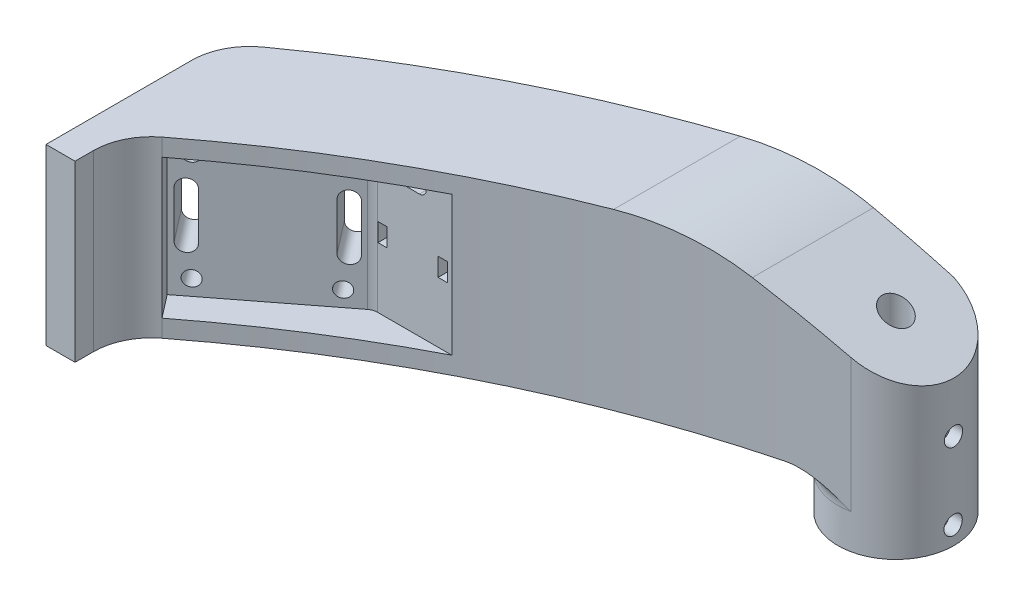
SolidWorks part; units mm, degrees
ref_plane "Front Plane" through (0, 0, 0) normal (0, 0, 1) x (1, 0, 0)
ref_plane "Top Plane" through (0, 0, 0) normal (0, 1, 0) x (1, 0, 0)
ref_plane "Right Plane" through (0, 0, 0) normal (1, 0, 0) x (0, 0, -1)
sketch "Sketch1" plane through (0, 0, 0) normal (0, 1, 0) x (1, 0, 0)
  line L1 (0, 0) -> (-86.36, -49.86) construction
  line L2 (0, 0) -> (-70.9465, 0) construction
  line L3 (0, 0) -> (0, -166.0504) construction
  line L4 (-86.36, -49.86) -> (-35.56, -49.86) construction
  line L5 (-86.36, -49.86) -> (-86.36, -100.66) construction
  line L6 (-86.36, -100.66) -> (-35.56, -100.66) construction
  line L7 (-35.56, -49.86) -> (-35.56, -100.66) construction
  line L8 (-86.36, -49.86) -> (-35.56, -100.66) construction
  line L9 (-86.36, -100.66) -> (-35.56, -49.86) construction
  line L10 (-105.41, -63.9265) -> (-105.41, -74.0865)
  line L11 (-105.41, -74.0865) -> (-111.76, -74.0865)
  line L12 (-111.76, -74.0865) -> (-111.76, -35.8449)
  circle A0 centre (0, 0) radius 12.7
  arc A1 (2.611, -12.4287) -> (-105.41, -63.9265) centre (54.83, -261.003) ccw
  arc A2 (-111.76, -35.8449) -> (0, 12.7) centre (42.7575, -238.6554) cw
  point P12 (-60.96, -75.26)
  dimension "D1" = 25.4
  dimension "D7" = 254
  dimension "D10" = 25.4
  dimension "D11" = 254.9662
  dimension "D2" = 30
  dimension "D3" = 50.8
  dimension "D4" = 50.8
  dimension "2.5" = 60.96
  dimension "D6" = 19.05
  dimension "D8" = 6.35
  dimension "D9" = 10.16
extrude "Boss-Extrude1" add sketch "Sketch1" along normal blind 38.1 contours A1 A0 L12 L11 L10 | A0 region at (-63.4576, 0, 24.428) region at (0.0025, 0, 0.0139)
sketch "Sketch3" plane through (0, 0, 0) normal (0, 0, 1) x (1, 0, 0)
  line L0 (-111.76, 19.05) -> (12.7, 19.05) construction
  line L1 (-111.76, 38.1) -> (-111.76, 0) construction
  line L2 (12.7, 0) -> (12.7, 38.1) construction
  line L4 (-115.2153, 16.5219) -> (-96.2951, 16.5219)
  line L5 (-115.2153, 16.5219) -> (-115.2153, 21.5781)
  line L6 (-115.2153, 21.5781) -> (-96.2951, 21.5781)
  line L7 (-96.2951, 16.5219) -> (-96.2951, 21.5781)
  line L8 (-115.2153, 16.5219) -> (-96.2951, 21.5781) construction
  line L9 (-115.2153, 21.5781) -> (-96.2951, 16.5219) construction
  point P6 (-105.7552, 19.05)
fillet "Fillet4" radius 12.7 1 edges at (-105.41, 19.05, 63.9265)
fillet "Fillet5" radius 12.7 1 edges at (-111.76, 19.05, 35.8449)
sketch "Sketch14" plane through (0, 0, 0) normal (0, -1, 0) x (1, 0, 0)
  circle A0 centre (0, 0) radius 10.125
  dimension "D1" = 20.25
extrude "Cut-Extrude9" cut sketch "Sketch14" against normal blind 12
sketch "Sketch16" plane through (0, 0, 0) normal (0, -1, 0) x (1, 0, 0)
  circle A0 centre (0, 0) radius 12.7
  circle A1 centre (0, 0) radius 10
  dimension "D1" = 20
  dimension "D2" = 25.4
extrude "Boss-Extrude2" add sketch "Sketch16" along normal blind 12.7
sketch "Sketch15" plane through (0, 0, 0) normal (1, 0, 0) x (0, 0, -1)
  line L0 (0, 0) -> (0.1356, 38.1) construction
  line L1 (12.7, 38.1) -> (-12.4287, 38.1) construction
  line L2 (-12.7, -12.7) -> (12.7, -12.7) construction
  circle A0 centre (-0.0312, -8.763) radius 2
  circle A1 centre (0.0285, 7.997) radius 2
  dimension "D2" = 4
  dimension "D3" = 4
  dimension "D1" = 16.76
  dimension "D4" = 3.937
extrude "Cut-Extrude10" cut sketch "Sketch15" along normal through all
sketch "Sketch17" plane through (0, 0, 0) normal (0, 0, 1) x (1, 0, 0)
  line L0 (0, -12.7) -> (0, -4.449) construction
  line L1 (-12.7, -12.7) -> (12.7, -12.7) construction
pattern_circular "CirPattern1" count 2 over 90 about axis through (0, -12.7, 0) along (0, 1, 0) of "Cut-Extrude10"
sketch "Sketch18" plane through (0, 0, 0) normal (0, 1, 0) x (1, 0, 0)
  line L2 (-100.4753, -60.0148) -> (-13.9089, 6.8758) construction
  arc A1 (2.611, -12.4287) -> (-100.4753, -60.0148) centre (54.83, -261.003) ccw construction
ref_plane "Plane2" through (-8.5266, 0, -11.0347) normal (0.6114, 0, 0.7913) x (0.7913, 0, -0.6114)
sketch "Sketch21" plane through (-8.5266, 0, -11.0347) normal (0.6114, 0, 0.7913) x (0.7913, 0, -0.6114)
  line L0 (-116.2006, 38.1) -> (-116.2006, 0) construction
  line L1 (-116.2006, 34.29) -> (-70.4806, 34.29)
  line L2 (-116.2006, 34.29) -> (-116.2006, 3.81)
  line L3 (-116.2006, 3.81) -> (-70.4806, 3.81)
  line L4 (-70.4806, 34.29) -> (-70.4806, 3.81)
  line L5 (-128.7094, 19.05) -> (-70.4806, 19.05) construction
  line L6 (-128.7094, 38.1) -> (-128.7094, 0) construction
  point P10 (-70.4806, 19.05)
  dimension "D1" = 30.48
  dimension "D2" = 45.72
extrude "Cut-Extrude11" cut sketch "Sketch21" along normal mid plane 12.7
sketch "Sketch22" plane through (-12.4093, 0, -16.0594) normal (0.6114, 0, 0.7913) x (0.7913, 0, -0.6114)
  line L1 (-112.3906, 7.239) -> (-88.7686, 7.239) construction
  line L2 (-112.3906, 7.239) -> (-112.3906, 30.861) construction
  line L3 (-112.3906, 30.861) -> (-88.7686, 30.861) construction
  line L4 (-88.7686, 7.239) -> (-88.7686, 30.861) construction
  line L5 (-112.3906, 7.239) -> (-88.7686, 30.861) construction
  line L6 (-112.3906, 30.861) -> (-88.7686, 7.239) construction
  line L7 (-133.7341, 19.05) -> (-107.4071, 19.05) construction
  line L8 (-114.9306, 4.699) -> (-86.2286, 4.699) construction
  line L9 (-114.9306, 4.699) -> (-114.9306, 33.401) construction
  line L10 (-114.9306, 33.401) -> (-86.2286, 33.401) construction
  line L11 (-86.2286, 4.699) -> (-86.2286, 33.401) construction
  line L12 (-114.9306, 4.699) -> (-86.2286, 33.401) construction
  line L13 (-114.9306, 33.401) -> (-86.2286, 4.699) construction
  line L14 (-133.7341, 38.1) -> (-133.7341, 0) construction
  line L15 (-116.2006, 34.29) -> (-116.2006, 3.81) construction
  circle A0 centre (-112.3906, 30.861) radius 1.651
  circle A1 centre (-88.7686, 30.861) radius 1.651
  circle A2 centre (-88.7686, 7.239) radius 1.651
  circle A3 centre (-112.3906, 7.239) radius 1.651
  point P0 (-100.5796, 19.05)
  point P9 (-100.5796, 19.05)
  dimension "D3" = 3.302
  dimension "D4" = 3.302
  dimension "D5" = 3.302
  dimension "D6" = 3.302
  dimension "D1" = 23.622
  dimension "D2" = 23.622
  dimension "D7" = 28.702
  dimension "D8" = 28.702
  dimension "D9" = 1.27
extrude "Cut-Extrude12" cut sketch "Sketch22" against normal through all
ref_plane "Plane3" through (-17.8449, 0, -23.094) normal (0.6114, 0, 0.7913) x (0.7913, 0, -0.6114)
sketch "Sketch23" plane through (-17.8449, 0, -23.094) normal (0.6114, 0, 0.7913) x (0.7913, 0, -0.6114)
  line L1 (-116.2006, 34.29) -> (-45.0806, 34.29)
  line L2 (-116.2006, 34.29) -> (-116.2006, 3.81)
  line L3 (-116.2006, 3.81) -> (-45.0806, 3.81)
  line L4 (-45.0806, 34.29) -> (-45.0806, 3.81)
  dimension "D1" = 71.12
extrude "Cut-Extrude13" cut sketch "Sketch23" against normal through all
sketch "Sketch24" plane through (-12.4093, 0, -16.0594) normal (0.6114, 0, 0.7913) x (0.7913, 0, -0.6114)
  line L0 (-87.8161, 24.257) -> (-87.8161, 13.97) construction
  line L1 (-70.4806, 34.29) -> (-70.4806, 3.81) construction
  line L2 (-116.2006, 3.81) -> (-70.4806, 3.81) construction
  line L3 (-85.9111, 24.257) -> (-85.9111, 13.97)
  line L4 (-89.7211, 24.257) -> (-89.7211, 13.97)
  line L5 (-113.2161, 24.257) -> (-113.2161, 13.97) construction
  line L8 (-111.3111, 24.257) -> (-111.3111, 13.97)
  line L9 (-115.1211, 24.257) -> (-115.1211, 13.97)
  arc A0 (-85.9111, 24.257) -> (-89.7211, 24.257) centre (-87.8161, 24.257) ccw
  arc A1 (-89.7211, 13.97) -> (-85.9111, 13.97) centre (-87.8161, 13.97) ccw
  arc A2 (-111.3111, 24.257) -> (-115.1211, 24.257) centre (-113.2161, 24.257) ccw
  arc A3 (-115.1211, 13.97) -> (-111.3111, 13.97) centre (-113.2161, 13.97) ccw
  point P2 (-85.9111, 19.1135)
  point P6 (-87.8161, 19.1135)
  point P11 (-113.2161, 19.1135)
  dimension "D1" = 3.81
  dimension "D2" = 25.4
  dimension "D3" = 10.287
  dimension "D4" = 15.4305
  dimension "D5" = 10.16
  dimension "D6" = 3.81
  dimension "D7" = 10.287
extrude "Cut-Extrude14" cut sketch "Sketch24" against normal through all contours L3 A1 L4 A0 | L8 A3 L9 A2
fillet "Fillet6" radius 5.08 1 edges at (-12.2026, 0, 3.5196)
ref_plane "Plane5" through (0, 0, 35.3426) normal (0, 0, 1) x (1, 0, 0)
sketch "Sketch25" plane through (0, 0, 35.3426) normal (0, 0, 1) x (1, 0, 0)
  line L0 (-68.18, 34.29) -> (-104.3579, 34.29) construction
  line L1 (-61.7607, 3.81) -> (-79.5407, 3.81)
  line L2 (-61.7607, 3.81) -> (-61.7607, 34.29)
  line L3 (-61.7607, 34.29) -> (-79.5407, 34.29)
  line L4 (-79.5407, 3.81) -> (-79.5407, 34.29)
  dimension "D1" = 17.78
extrude "Boss-Extrude3" add sketch "Sketch25" against normal up to body
sketch "Sketch26" plane through (0, 0, 35.3426) normal (0, 0, 1) x (1, 0, 0)
  line L0 (-70.346, 34.29) -> (-70.346, 3.81) construction
  line L1 (-61.7607, 34.29) -> (-78.9312, 34.29) construction
  line L2 (-78.9312, 3.81) -> (-61.7607, 3.81) construction
  line L3 (-71.846, 32.29) -> (-68.846, 32.29) construction
  line L4 (-71.846, 33.79) -> (-68.846, 33.79)
  line L5 (-71.846, 30.79) -> (-68.846, 30.79)
  line L6 (-100.4753, 34.29) -> (-61.7607, 34.29) construction
  line L7 (-70.346, 19.05) -> (-61.7607, 19.05) construction
  line L8 (-77.9152, 21.05) -> (-75.9152, 21.05)
  line L9 (-77.9152, 21.05) -> (-77.9152, 17.05)
  line L10 (-77.9152, 17.05) -> (-75.9152, 17.05)
  line L11 (-75.9152, 21.05) -> (-75.9152, 17.05)
  line L12 (-64.7607, 21.05) -> (-62.7607, 21.05)
  line L13 (-64.7607, 21.05) -> (-64.7607, 17.05)
  line L14 (-64.7607, 17.05) -> (-62.7607, 17.05)
  line L15 (-62.7607, 21.05) -> (-62.7607, 17.05)
  line L16 (-61.7607, 34.29) -> (-61.7607, 3.81) construction
  line L17 (-70.346, 19.05) -> (-88.3378, 19.05) construction
  line L20 (-78.9312, 3.81) -> (-78.9312, 34.29) construction
  arc A0 (-71.846, 33.79) -> (-71.846, 30.79) centre (-71.846, 32.29) ccw
  arc A1 (-68.846, 30.79) -> (-68.846, 33.79) centre (-68.846, 32.29) ccw
  point P8 (-70.346, 32.29)
  point P13 (-67.346, 32.29)
  point P14 (-73.346, 32.29)
  point P29 (-75.9152, 19.05)
  point P33 (-62.7607, 19.05)
  dimension "D1" = 6
  dimension "D2" = 3
  dimension "D3" = 2
  dimension "D4" = 2
  dimension "D5" = 4
  dimension "D6" = 4
  dimension "D7" = 2
  dimension "D8" = 1.016
  dimension "D9" = 1
extrude "Cut-Extrude15" cut sketch "Sketch26" against normal through all
fillet "Fillet8" radius 2.54 1 edges at (-78.9312, 19.05, 35.3426)
sketch "Sketch27" plane through (0, 0, 0) normal (0, 0, 1) x (1, 0, 0)
  line L0 (-25.4, 38.1) -> (12.7, 19.05)
  line L1 (2.611, 38.1) -> (-100.4753, 38.1) construction
  line L2 (12.7, 9.9968) -> (12.7, 38.1) construction
  line L3 (12.7, 19.05) -> (12.7, 38.1)
  line L4 (12.7, 38.1) -> (-25.4, 38.1)
  dimension "D1" = 19.05
  dimension "D2" = 38.1
extrude "Cut-Extrude16" cut sketch "Sketch27" against normal through all both and the other way through all
fillet "Fillet9" radius 50.8 1 edges at (-25.4, 38.1, 6.4874)
sketch "Sketch28" plane through (0, 12, 0) normal (0, -1, 0) x (-1, 0, 0)
  circle A0 centre (0, 0) radius 3
  dimension "D1" = 6
extrude "Cut-Extrude17" cut sketch "Sketch28" against normal through all both and the other way through all
